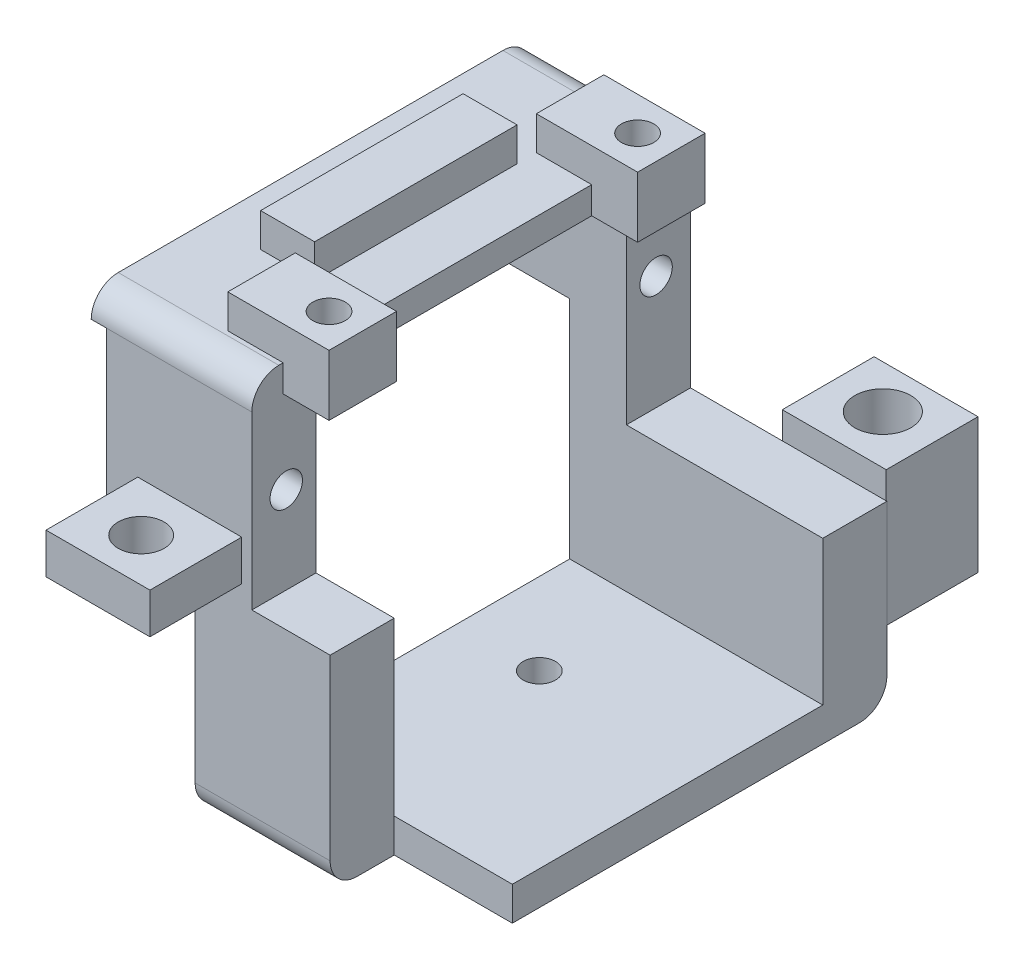
SolidWorks part; units mm, degrees
ref_plane "Front Plane" through (0, 0, 0) normal (0, 0, 1) x (1, 0, 0)
ref_plane "Top Plane" through (0, 0, 0) normal (0, 1, 0) x (1, 0, 0)
ref_plane "Right Plane" through (0, 0, 0) normal (1, 0, 0) x (0, 0, -1)
sketch "Sketch1" plane through (0, 0, 0) normal (0, 1, 0) x (1, 0, 0)
  line L0 (-1.1, 16.25) -> (-1.1, 11.5)
  line L1 (-17.65, -16.25) -> (17.65, -16.25)
  line L2 (-17.65, -16.25) -> (-17.65, 16.25)
  line L3 (-17.65, 16.25) -> (17.65, 16.25)
  line L4 (17.65, -16.25) -> (17.65, 16.25)
  line L5 (-17.65, -16.25) -> (17.65, 16.25) construction
  line L6 (-17.65, 16.25) -> (17.65, -16.25) construction
  line L7 (-1.1, 11.5) -> (17.65, 11.5)
  line L8 (-1.1, -16.25) -> (-1.1, -11.5)
  line L9 (-1.1, -11.5) -> (17.65, -11.5)
  line L10 (-1.1, 11.5) -> (-1.1, -11.5) construction
  line L11 (8.9, -11.5) -> (8.9, -16.25)
  line L12 (-8.8, 16.25) -> (-8.8, 11.5)
  line L13 (-8.8, 11.5) -> (-3.8, 11.5)
  line L14 (-3.8, 11.5) -> (-3.8, 16.25)
  line L15 (-3.8, -16.25) -> (-3.8, -11.5)
  line L16 (-3.8, -11.5) -> (-8.8, -11.5)
  line L17 (-8.8, -11.5) -> (-8.8, -16.25)
  line L18 (-8.8, 11.5) -> (-8.8, -11.5)
  line L19 (17.6, 16.25) -> (17.6, 23.05)
  line L20 (17.6, 23.05) -> (9.9, 23.05)
  line L21 (9.9, 23.05) -> (9.9, 16.25)
  line L22 (-5.35, -16.25) -> (-5.35, -23.05)
  line L23 (-5.35, -23.05) -> (2.35, -23.05)
  line L24 (2.35, -23.05) -> (2.35, -16.25)
  line L28 (-1.1, 11.5) -> (-1.1, -11.5)
  circle A0 centre (13.75, 19.85) radius 2.075
  circle A2 centre (-1.5, -19.85) radius 1.7
  point P0 (0, 0)
  point P11 (-1.1, 0)
  point P31 (13.75, 23.05)
  point P45 (-1.5, -23.05)
  dimension "D11" = 4.15
  dimension "D19" = 3.4
  dimension "D1" = 32.5
  dimension "D2" = 23
  dimension "D3" = 8.75
  dimension "D4" = 10
  dimension "D5" = 16.55
  dimension "D6" = 2.7
  dimension "D7" = 5
  dimension "D8" = 13.75
  dimension "D9" = 7.7
  dimension "D10" = 6.8
  dimension "D12" = 1.5
  dimension "D13" = 19.85
  dimension "D16" = 7.7
  dimension "D17" = 6.8
  dimension "D20" = 19.85
extrude "Boss-Extrude1" add sketch "Sketch1" against normal blind 2.5 contours L7 L28 L9 L4 | L0 L7 L4 L3 | L11 L9 L8 L1 region at (8.275, 0, -13.875) region at (8.275, 0, 0) region at (3.9, 0, 13.875)
extrude "Boss-Extrude2" add sketch "Sketch1<3>" along normal blind 12.7 contours L0 L7 L4 L3 | L11 L9 L8 L1 region at (8.275, 0, -13.875) region at (3.9, 0, 13.875)
sketch "Sketch1<3>" plane through (0, 0, 0) normal (0, 1, 0) x (1, 0, 0) same geometry as "Sketch1"
sketch "Sketch3" plane through (0, 0, 0) normal (0, 1, 0) x (1, 0, 0)
  line L0 (3.1, 16.25) -> (3.1, 11.5)
  line L1 (-17.65, 16.25) -> (17.65, 16.25) construction
  line L2 (-1.1, 11.5) -> (17.65, 11.5) construction
  line L3 (3.1, 11.5) -> (-17.65, 11.5)
  line L4 (-17.65, -16.25) -> (-17.65, 16.25) construction
  line L5 (3.1, -16.25) -> (3.1, -11.5)
  line L6 (-17.65, -16.25) -> (17.65, -16.25) construction
  line L7 (-1.1, -11.5) -> (17.65, -11.5) construction
  line L8 (3.1, -11.5) -> (-17.65, -11.5)
  line L9 (3.1, 11.5) -> (3.1, -11.5)
  line L10 (-7.65, -11.5) -> (-7.65, -16.275)
  line L11 (3.1, 16.25) -> (-17.65, 16.25)
  line L12 (-17.65, 16.25) -> (-17.65, 11.5)
  line L13 (-17.65, -11.5) -> (-17.65, -16.25)
  line L14 (-17.65, -16.25) -> (3.1, -16.25)
  line L15 (-8.8, 11.5) -> (-8.8, -11.5)
  line L16 (-8.8, 11.5) -> (-8.8, 16.25)
  line L17 (-8.8, -11.5) -> (-8.8, -16.25)
  dimension "D1" = 20.75
  dimension "D2" = 10
extrude "Boss-Extrude3" add sketch "Sketch3" along normal blind 12.7 from surface contours L11 L12 L3 L0 | L10 L14 L5 L8 region at (-2.85, 0, -13.875) region at (-2.275, 0, 13.875) starting at face at (8.275, 12.7, -13.875)
extrude "Boss-Extrude4" add sketch "Sketch3<3>" along normal blind 2 from surface contours L16 L3 L0 L11 | L3 L15 L8 L9 | L10 L14 L5 L8 | L8 L17 L14 L10 region at (-2.85, 0, -13.875) region at (-2.85, 0, 0) region at (-2.275, 0, 13.875) region at (-8.225, 0, 13.875) starting at face at (-2.275, 25.4, 13.875)
sketch "Sketch3<3>" plane through (0, 0, 0) normal (0, 1, 0) x (1, 0, 0) same geometry as "Sketch3"
sketch "Sketch2" plane through (0, 0, 0) normal (1, 0, 0) x (0, 0, -1)
  line L0 (13.7, 6.45) -> (-13.7, 6.45) construction
  line L1 (-13.7, 19.15) -> (13.7, 19.15) construction
  circle A0 centre (13.7, 6.45) radius 1.2
  circle A1 centre (-13.7, 6.45) radius 1.2
  circle A2 centre (-13.7, 19.15) radius 1.2
  circle A3 centre (13.7, 19.15) radius 1.2
  point P4 (0, 6.45)
  dimension "D1" = 2.4
  dimension "D2" = 2.4
  dimension "D6" = 2.4
  dimension "D7" = 2.4
  dimension "D3" = 27.4
  dimension "D4" = 6.45
  dimension "D5" = 6.45
extrude "Cut-Extrude1" cut sketch "Sketch2" along normal blind 8 from surface contours A1 | A0 region at (0, 6.45, -13.7) region at (0, 6.45, 13.7) starting at face at (-1.1, 5.725, 0)
extrude "Cut-Extrude2" cut sketch "Sketch2<3>" against normal blind 8 from surface contours A3 | A2 region at (0, 19.15, 13.7) region at (0, 19.15, -13.7) starting at face at (3.1, 19.55, 0)
sketch "Sketch2<3>" plane through (0, 0, 0) normal (1, 0, 0) x (0, 0, -1) same geometry as "Sketch2"
extrude "Boss-Extrude5" add sketch "Sketch1<4>" against normal blind 3 from offset 17 contours L23 L24 L1 L22 A2 region at (0.625, 0, 16.3527)
sketch "Sketch1<4>" plane through (0, 0, 0) normal (0, 1, 0) x (1, 0, 0) same geometry as "Sketch1"
extrude "Boss-Extrude6" add sketch "Sketch1<7>" against normal blind 10 from surface contours L20 L21 L3 L19 A0 region at (10.0027, 0, -19.65) starting at face at (10.375, 12.7, -13.875)
sketch "Sketch1<7>" plane through (0, 0, 0) normal (0, 1, 0) x (1, 0, 0) same geometry as "Sketch1"
fillet "Fillet1" radius 2 4 edges at (3.9, -2.5, 16.25) (-2.85, 27.4, 16.25) (8.275, -2.5, -16.25) (-2.85, 27.4, -16.25)
sketch "Sketch5" plane through (0, 0, 0) normal (0, 1, 0) x (1, 0, 0)
  line L1 (17.65, 16.25) -> (3.1, 16.25)
  line L2 (17.65, 16.25) -> (17.65, 11.5)
  line L3 (17.65, 11.5) -> (3.1, 11.5)
  line L4 (3.1, 16.25) -> (3.1, 11.5)
extrude "Cut-Extrude3" cut sketch "Sketch5" against normal blind 2 from surface starting at face at (12.0625, 12.7, -16.7625)
sketch "Sketch6" plane through (0, 0, 0) normal (0, 1, 0) x (1, 0, 0)
  line L1 (-8.8, 11.5) -> (-1.1, 11.5)
  line L2 (-8.8, 11.5) -> (-8.8, 16.25)
  line L3 (-8.8, 16.25) -> (-1.1, 16.25)
  line L4 (-1.1, 11.5) -> (-1.1, 16.25)
extrude "Cut-Extrude4" cut sketch "Sketch6" along normal blind 4 from surface starting at face at (-4.95, 12.7, -13.875)
sketch "Sketch7" plane through (0, 0, 0) normal (0, 1, 0) x (1, 0, 0)
  line L0 (4, 11.43) -> (4, -11.43) construction
  line L2 (1.5, 13.93) -> (6.5, 13.93)
  line L3 (1.5, 13.93) -> (1.5, 8.93)
  line L4 (1.5, 8.93) -> (6.5, 8.93)
  line L5 (6.5, 13.93) -> (6.5, 8.93)
  line L6 (1.5, 13.93) -> (6.5, 8.93) construction
  line L7 (1.5, 8.93) -> (6.5, 13.93) construction
  line L8 (1.5, -8.93) -> (6.5, -8.93)
  line L9 (1.5, -8.93) -> (1.5, -13.93)
  line L10 (1.5, -13.93) -> (6.5, -13.93)
  line L11 (6.5, -8.93) -> (6.5, -13.93)
  line L12 (1.5, -8.93) -> (6.5, -13.93) construction
  line L13 (1.5, -13.93) -> (6.5, -8.93) construction
  line L21 (-5, -7.5) -> (-1, -7.5)
  line L22 (-5, -7.5) -> (-5, 7.5)
  line L23 (-5, 7.5) -> (-1, 7.5)
  line L24 (-1, -7.5) -> (-1, 7.5)
  line L25 (-5, -7.5) -> (-1, 7.5) construction
  line L26 (-5, 7.5) -> (-1, -7.5) construction
  line L27 (1.5, 13.93) -> (-1, 13.93)
  line L28 (1.5, 13.93) -> (1.5, 8.93)
  line L29 (1.5, 8.93) -> (-1, 8.93)
  line L30 (-1, 13.93) -> (-1, 8.93)
  line L31 (1.5, -13.93) -> (-1, -13.93)
  line L32 (1.5, -13.93) -> (1.5, -8.93)
  line L33 (1.5, -8.93) -> (-1, -8.93)
  line L34 (-1, -13.93) -> (-1, -8.93)
  circle A0 centre (4, 11.43) radius 1.2
  circle A1 centre (4, -11.43) radius 1.2
  point P4 (4, 0)
  point P14 (-3, 0)
  dimension "D1" = 2.4
  dimension "D2" = 2.4
  dimension "D3" = 22.86
  dimension "D4" = 5
  dimension "D5" = 5
  dimension "D6" = 5
  dimension "D7" = 5
  dimension "D8" = 4
  dimension "D9" = 3
  dimension "D10" = 15
  dimension "D11" = 4
extrude "Boss-Extrude7" add sketch "Sketch7" along normal blind 2.5 and the other way blind 2 from surface contours L21 L24 L23 L22 | L11 L8 L9 L10 A1 | L34 L31 L9 L33 | L27 L30 L29 L3 | L5 L2 L3 L4 A0 region at (4, 0, -13.8593) region at (0.25, 0, -11.43) region at (4, 0, 9.0007) region at (0.25, 0, 11.43) region at (-3, 0, 0) starting at face at (-2.85, 27.4, 0)
sketch "Sketch8" plane through (0, 0, 0) normal (0, 1, 0) x (1, 0, 0)
  line L2 (-17.65, -16.25) -> (17.65, -16.25) construction
  line L3 (7.45, 5.7) -> (2.45, 5.7)
  line L4 (7.45, 5.7) -> (7.45, 0.7)
  line L5 (7.45, 0.7) -> (2.45, 0.7)
  line L6 (2.45, 5.7) -> (2.45, 0.7)
  line L7 (7.45, 5.7) -> (2.45, 0.7) construction
  line L8 (7.45, 0.7) -> (2.45, 5.7) construction
  line L11 (-1.1, 11.5) -> (-1.1, -11.5) construction
  circle A0 centre (4.95, 3.2) radius 1.2
  dimension "D3" = 2.4
  dimension "D1" = 6.05
  dimension "D2" = 19.45
  dimension "D4" = 5
  dimension "D5" = 5
extrude "Boss-Extrude8" add sketch "Sketch8" against normal blind 4.1 from surface starting at face at (8.4833, -2.5, 3.8333)
extrude "Cut-Extrude5" cut sketch "Sketch8<2>" against normal through all both contours A0 region at (4.95, 0, -3.2)
sketch "Sketch8<2>" plane through (0, 0, 0) normal (0, 1, 0) x (1, 0, 0) same geometry as "Sketch8"
extrude "Cut-Extrude6" cut sketch "Sketch7<4>" along normal up to surface (29.9 mm away) from surface contours A0 | A1 region at (4, 0, -11.43) region at (4, 0, 11.43) up to face at (4, 29.9, 10.23) starting at face at (1.5722, 25.4, 1.8056)
sketch "Sketch7<4>" plane through (0, 0, 0) normal (0, 1, 0) x (1, 0, 0) same geometry as "Sketch7"
